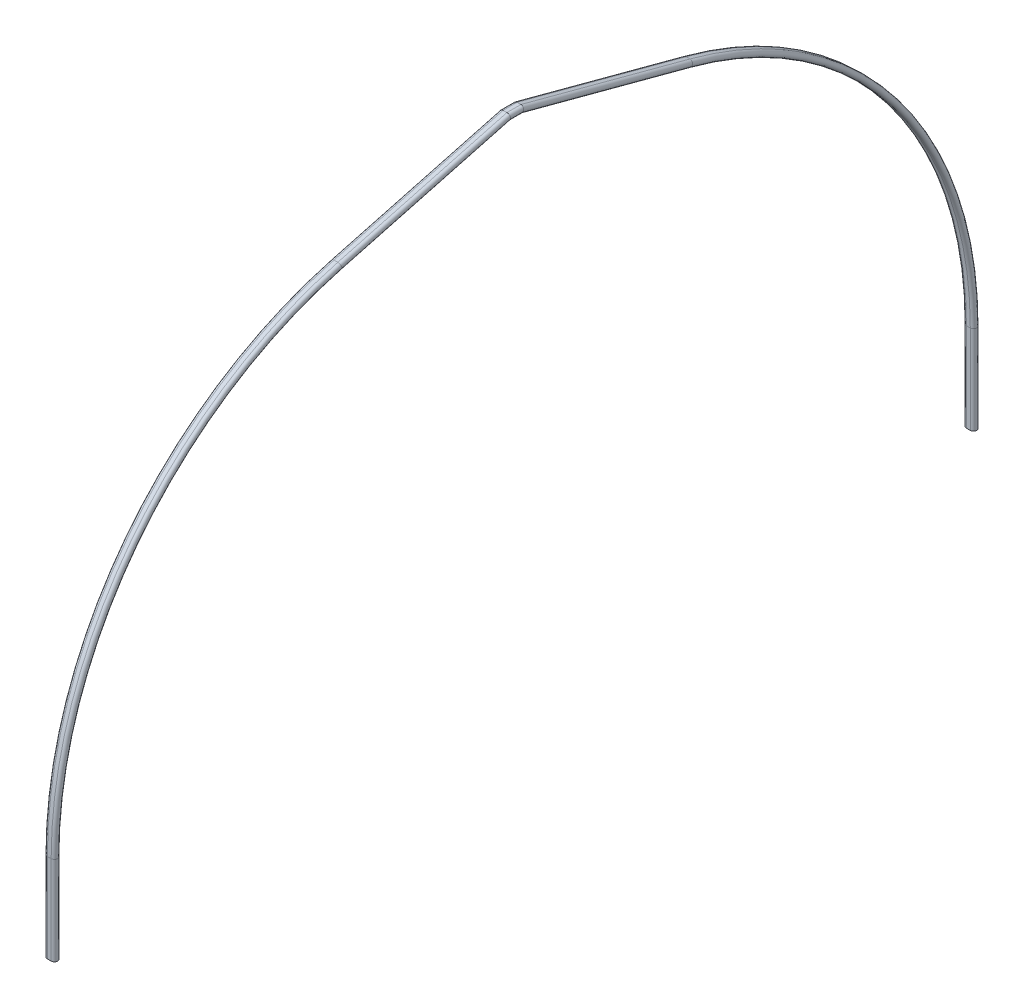
SolidWorks part; units mm, degrees
ref_plane "Front Plane" through (0, 0, 0) normal (0, 0, 1) x (1, 0, 0)
ref_plane "Top Plane" through (0, 0, 0) normal (0, 1, 0) x (1, 0, 0)
ref_plane "Right Plane" through (0, 0, 0) normal (1, 0, 0) x (0, 0, -1)
sketch "Sketch1" plane through (0, 0, 0) normal (0, 1, 0) x (1, 0, 0)
  line L0 (0, 0) -> (38.1, 0) construction
  line L1 (0, 31.75) -> (38.1, 31.75)
  line L2 (0, -31.75) -> (38.1, -31.75)
  line L3 (0, 0) -> (38.1, 0) construction
  line L4 (0, 20.3048) -> (38.1, 20.3048)
  line L5 (0, -20.3048) -> (38.1, -20.3048)
  arc A0 (0, 31.75) -> (0, -31.75) centre (0, 0) ccw
  arc A1 (38.1, -31.75) -> (38.1, 31.75) centre (38.1, 0) ccw
  arc A2 (0, 20.3048) -> (0, -20.3048) centre (0, 0) ccw
  arc A3 (38.1, -20.3048) -> (38.1, 20.3048) centre (38.1, 0) ccw
  point P3 (19.05, 0)
  point P10 (19.05, 0)
  dimension "D1" = 38.1
  dimension "D2" = 63.5
sketch "Sketch4" plane through (0, 0, 0) normal (1, 0, 0) x (0, 0, -1)
  line L0 (0, 0) -> (0, 882.8596)
  line L1 (6315.6947, 4564.2147) -> (4637.4463, 5011.7476)
  line L2 (0, 0) -> (4572, 0) construction
  line L3 (4572, 0) -> (4572, 5029.2) construction
  line L4 (2828.3053, 4564.2147) -> (4506.5537, 5011.7476)
  line L5 (9144, 0) -> (9144, 882.8596)
  line L6 (0, 3810) -> (7772.8418, 3810) construction
  line L7 (4506.5537, 5011.7476) -> (4637.4463, 5011.7476)
  arc A0 (0, 882.8596) -> (2828.3053, 4564.2147) centre (3810, 882.8596) cw
  arc A1 (9144, 882.8596) -> (6315.6947, 4564.2147) centre (5334, 882.8596) ccw
  point P8 (0, 3810)
  dimension "D2" = 4572
  dimension "D4" = 3810
  dimension "D1" = 3810
  dimension "D3" = 5029.2
sweep "Sweep1" add profiles "Sketch1" path "Sketch4"
sketch3d "3DSketch8"
  line L0 (0, 4979.9976, -4633.2857) -> (0, 4979.9976, -4510.7143) construction
  line L1 (38.1, 4979.9976, -4633.2857) -> (38.1, 4979.9976, -4510.7143) construction
  line L2 (0, 4979.9976, -4572) -> (0, 4979.9976, -4552.95)
  line L3 (0, 4979.9976, -4572) -> (0, 4979.9976, -4591.05)
  line L4 (38.1, 4979.9976, -4572) -> (38.1, 4979.9976, -4591.05)
  line L5 (38.1, 4979.9976, -4572) -> (38.1, 4979.9976, -4552.95)
  line L6 (19.05, 4979.9976, -4510.7143) -> (19.05, 4979.9976, -4633.2857) construction
  line L7 (0, 4979.9976, -4510.7143) -> (38.1, 4979.9976, -4510.7143) construction
  line L8 (0, 4979.9976, -4633.2857) -> (38.1, 4979.9976, -4633.2857) construction
  circle A0 centre (0, 4979.9976, -4552.95) radius 6.35
  circle A1 centre (0, 4979.9976, -4591.05) radius 6.35
  circle A2 centre (38.1, 4979.9976, -4591.05) radius 6.35
  circle A3 centre (38.1, 4979.9976, -4552.95) radius 6.35
  point P0 (18.6117, 4979.9976, -4560.4976)
  point P12 (0, 4986.3476, -4552.95)
  point P15 (0, 4986.3476, -4591.05)
  point P20 (38.1, 4986.3476, -4591.05)
  point P22 (38.1, 4986.3476, -4552.95)
  dimension "D2" = 12.7
  dimension "D4" = 12.7
  dimension "D7" = 12.7
  dimension "D8" = 12.7
  dimension "D1" = 19.05
  dimension "D3" = 19.05
  dimension "D5" = 19.05
  dimension "D6" = 19.05
ref_plane "Plane10" through (0, 4979.9976, 0) normal (0, -1, 0) x (1, 0, 0)
extrude "Cut-Extrude1" cut sketch "3DSketch8" along direction (0, 1, 0) on the side of the normal blind 25.4 contours A3 | A0 | A1 | A2
sketch3d "3DSketch11"
  point P0 (23.8265, 4873.2573, -4110.438)
ref_plane "Plane13" through (0, 3526.376, 940.3669) normal (0, -0.9662, -0.2577) x (1, 0, 0)
sketch "Sketch5" plane through (0, 3526.376, 940.3669) normal (0, -0.9662, -0.2577) x (1, 0, 0)
  line L0 (0, -5641.5692) -> (0, -3908.8351) construction
  line L1 (0, -5080.1584) -> (38.1, -5080.1584) construction
  line L2 (38.1, -5641.5692) -> (38.1, -3908.8351) construction
  line L3 (19.05, -5080.1584) -> (19.05, -5129.4035) construction
  circle A0 centre (0, -5080.1584) radius 6.35
  circle A1 centre (0, -5288.4384) radius 6.35
  circle A2 centre (38.1, -5288.4384) radius 6.35
  circle A3 centre (38.1, -5080.1584) radius 6.35
  dimension "D1" = 12.7
  dimension "D2" = 12.7
  dimension "D3" = 208.28
extrude "Cut-Extrude2" cut sketch "Sketch5" against normal blind 12.7
